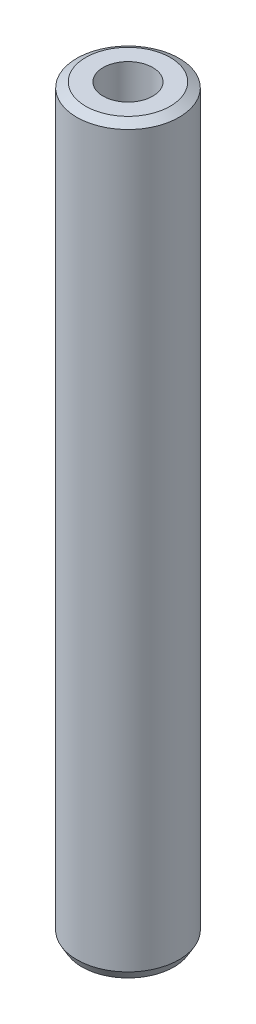
SolidWorks part; units mm, degrees
ref_plane "Front Plane" through (0, 0, 0) normal (0, 0, 1) x (1, 0, 0)
ref_plane "Top Plane" through (0, 0, 0) normal (0, 1, 0) x (1, 0, 0)
ref_plane "Right Plane" through (0, 0, 0) normal (1, 0, 0) x (0, 0, -1)
sketch "Sketch1" plane through (0, 0, 0) normal (0, 1, 0) x (1, 0, 0)
  circle A0 centre (0, 0) radius 5
  dimension "SHAFT_OD" = 10
extrude "Boss-Extrude1" add sketch "Sketch1" along normal blind 72.6724
sketch "Sketch2" plane through (0, 0, 0) normal (0, 1, 0) x (1, 0, 0)
  circle A0 centre (0, 0) radius 2.4262
  dimension "BORE_D" = 4.8524
extrude "Cut-Extrude1" cut sketch "Sketch2" along normal through all
chamfer "Chamfer1" distance 0.5016 angle 60 2 edges at (0, 72.6724, 5) (0, 0, 5) first distance on face at (0, 72.6724, 5) first distance on face at (0, 0, 2.4262)
